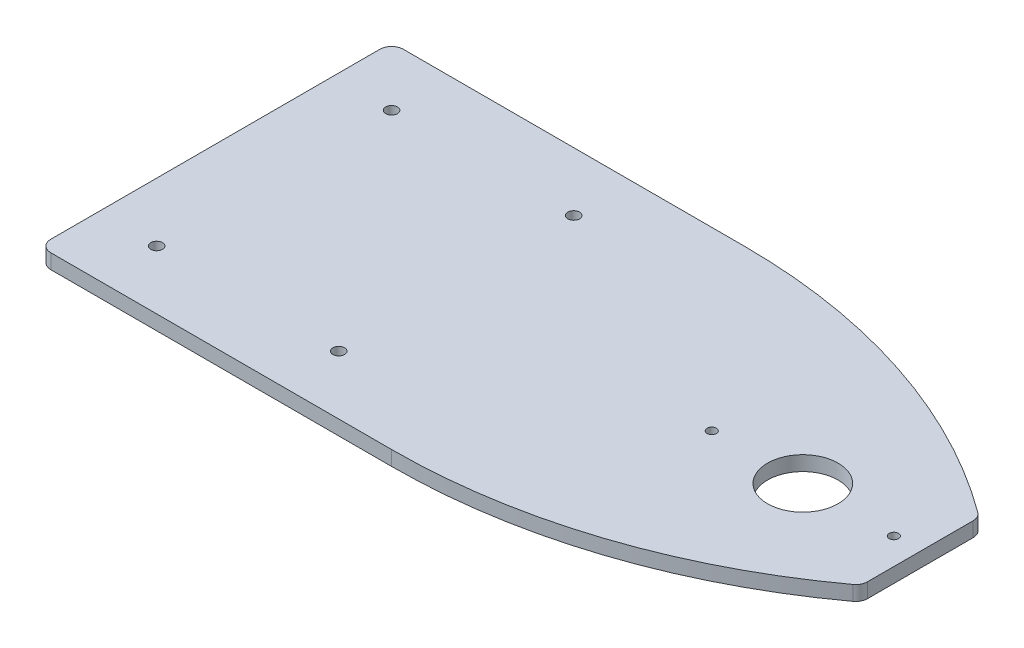
SolidWorks part; units mm, degrees
material "PLA"
ref_plane "Front" through (0, 0, 0) normal (0, 0, 1) x (1, 0, 0)
ref_plane "Top" through (0, 0, 0) normal (0, 1, 0) x (1, 0, 0)
ref_plane "Right" through (0, 0, 0) normal (1, 0, 0) x (0, 0, -1)
sketch "Sketch1" plane through (0, 0, 0) normal (0, 1, 0) x (1, 0, 0)
  line L1 (76.2, -38.1) -> (-76.2, -38.1)
  line L2 (76.2, -38.1) -> (76.2, 38.1)
  line L3 (76.2, 38.1) -> (-76.2, 38.1)
  line L4 (-76.2, -38.1) -> (-76.2, 38.1)
  line L5 (76.2, -38.1) -> (-76.2, 38.1) construction
  line L6 (76.2, 38.1) -> (-76.2, -38.1) construction
  point P0 (0, 0)
  dimension "D1" = 76.2
  dimension "D2" = 152.4
extrude "Boss-Extrude1" add sketch "Sketch1" along normal blind 3.175
sketch "Sketch4" plane through (0, 3.175, 0) normal (0, 1, 0) x (1, 0, 0)
  line L0 (0, 38.1) -> (76.2, 38.1)
  line L1 (76.2, 38.1) -> (-76.2, 38.1) construction
  line L2 (76.2, 38.1) -> (76.2, 12.7)
  line L3 (76.2, -38.1) -> (76.2, 38.1) construction
  line L4 (76.2, -38.1) -> (76.2, -12.7)
  line L5 (76.2, -38.1) -> (0, -38.1)
  line L6 (-76.2, -38.1) -> (76.2, -38.1) construction
  arc A0 (0, -38.1) -> (76.2, -12.7) centre (0, 88.9) ccw
  arc A1 (0, 38.1) -> (76.2, 12.7) centre (0, -88.9) cw
  dimension "D3" = 127
  dimension "D4" = 127
  dimension "D1" = 25.4
  dimension "D2" = 25.4
extrude "Cut-Extrude1" cut sketch "Sketch4" against normal blind 3.175
fillet "Fillet2" radius 2.54 2 edges at (76.2, 1.5875, 12.7) (76.2, 1.5875, -12.7)
fillet "Fillet3" radius 2.54 2 edges at (-76.2, 1.5875, 38.1) (-76.2, 1.5875, -38.1)
sketch "Sketch5" plane through (0, 3.175, 0) normal (0, 1, 0) x (1, 0, 0)
  line L0 (-55, 0) -> (55, 0) construction
  line L1 (76.2, -11.422) -> (76.2, 11.422) construction
  circle A0 centre (50.8, 0) radius 7.62
  dimension "D1" = 15.24
  dimension "D2" = 25.4
extrude "Cut-Extrude2" cut sketch "Sketch5" against normal blind 3.175
sketch "Sketch6" plane through (0, 3.175, 0) normal (0, 1, 0) x (1, 0, 0)
  line L0 (0, 38.1) -> (-73.66, 38.1) construction
  line L1 (-73.66, -38.1) -> (0, -38.1) construction
  line L2 (-76.2, 35.56) -> (-76.2, -35.56) construction
  circle A0 centre (-63.5, 25.4) radius 1.27
  circle A1 centre (-63.5, -25.4) radius 1.27
  circle A2 centre (-24.13, 25.4) radius 1.27
  circle A3 centre (-24.13, -25.4) radius 1.27
  dimension "D1" = 2.54
  dimension "D2" = 2.54
  dimension "D4" = 12.7
  dimension "D7" = 2.54
  dimension "D8" = 2.54
  dimension "D3" = 12.7
  dimension "D5" = 12.7
  dimension "D6" = 12.7
  dimension "D9" = 39.37
  dimension "D10" = 39.37
extrude "Cut-Extrude3" cut sketch "Sketch6" against normal blind 3.175
sketch "Sketch7" plane through (0, 3.175, 0) normal (0, 1, 0) x (1, 0, 0)
  line L0 (50.8, -7.62) -> (50.8, 7.62)
  line L1 (50.8, 0) -> (70.485, 0)
  line L2 (-1.7463, 0) -> (1.7463, 0) construction
  line L3 (50.8, 0) -> (31.115, 0)
  circle A0 centre (50.8, 0) radius 7.62 construction
  circle A1 centre (70.485, 0) radius 1.0033
  circle A2 centre (31.115, 0) radius 1.0033
  dimension "D3" = 2.0066
  dimension "D4" = 2.0066
  dimension "D1" = 19.685
  dimension "D2" = 19.685
extrude "Cut-Extrude4" cut sketch "Sketch7" against normal through all contours A2 | A1 region at (30.1401, 3.175, 0)
